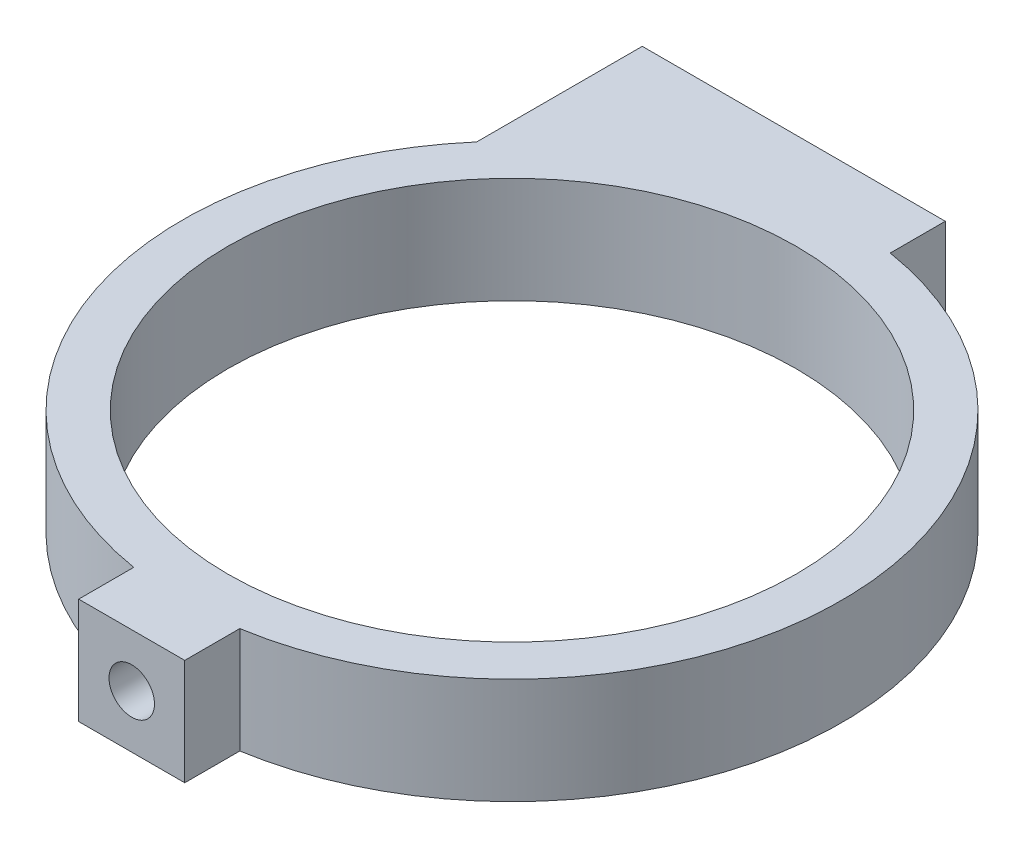
SolidWorks part; units mm, degrees
ref_plane "Front Plane" through (0, 0, 0) normal (0, 0, 1) x (1, 0, 0)
ref_plane "Top Plane" through (0, 0, 0) normal (0, 1, 0) x (1, 0, 0)
ref_plane "Right Plane" through (0, 0, 0) normal (1, 0, 0) x (0, 0, -1)
sketch "Sketch1" plane through (0, 0, 0) normal (0, 1, 0) x (1, 0, 0)
  line L0 (0, -20.1) -> (0, -25.1) construction
  line L1 (3.5, -25.1) -> (-3.5, -25.1)
  line L2 (-3.5, -25.1) -> (-3.5, -21.4665)
  line L3 (3.5, -25.1) -> (3.5, -21.4665)
  line L4 (0, 20.1) -> (0, 25.1) construction
  line L5 (3.5, 25.1) -> (-3.5, 25.1)
  line L6 (-3.5, 25.1) -> (-3.5, 21.4665)
  line L7 (3.5, 25.1) -> (3.5, 21.4665)
  circle A0 centre (0, 0) radius 18.75
  arc A1 (3.5, -21.4665) -> (3.5, 21.4665) centre (0, 0) ccw
  arc A2 (-3.5, 21.4665) -> (-3.5, -21.4665) centre (0, 0) ccw
  circle A3 centre (0, 0) radius 21.75 construction
  point P11 (19.2217, 5.8767)
  dimension "D1" = 3
  dimension "D3" = 3.5
  dimension "D2" = 5
  dimension "D4" = 5
  dimension "D5" = 3.5
extrude "Boss-Extrude1" add sketch "Sketch1" along normal blind 7 contours A1 L7 L5 L6 A2 L2 L1 L3 | A0
sketch "Sketch2" plane through (0, 0, 25.1) normal (0, 0, 1) x (1, 0, 0)
  line L0 (0, 7) -> (0, 0) construction
  line L1 (3.5, 7) -> (-3.5, 7) construction
  circle A0 centre (0, 3.5) radius 1.5
extrude "Cut-Extrude1" cut sketch "Sketch2" against normal blind 7
sketch "Sketch3" plane through (0, 0, -25.1) normal (0, 0, -1) x (-1, 0, 0)
  line L0 (0, 7) -> (0, 0) construction
  line L1 (-3.5, 7) -> (3.5, 7) construction
  circle A0 centre (0, 3.5) radius 1.4
extrude "Cut-Extrude2" cut sketch "Sketch3" against normal blind 5
sketch "Sketch6" plane through (0, 0, 0) normal (0, -1, 0) x (-1, 0, 0)
  line L0 (3.5, 25.1) -> (16.5, 25.1)
  line L1 (16.5, 25.1) -> (16.5, 14.1708)
  line L2 (3.5, 25.1) -> (3.5, 21.4665)
  arc A0 (3.5, -21.4665) -> (3.5, 21.4665) centre (0, 0) ccw construction
  arc A2 (16.5, 14.1708) -> (3.5, 21.4665) centre (0, 0) ccw
  dimension "D1" = 13
extrude "Boss-Extrude3" add sketch "Sketch6" against normal blind 7
sketch "Sketch7" plane through (0, 0, -25.1) normal (0, 0, -1) x (-1, 0, 0)
  line L0 (0, 3.5) -> (10, 3.5) construction
  circle A0 centre (10, 3.5) radius 1.4
  dimension "D1" = 10
extrude "Cut-Extrude3" cut sketch "Sketch7" against normal blind 7
